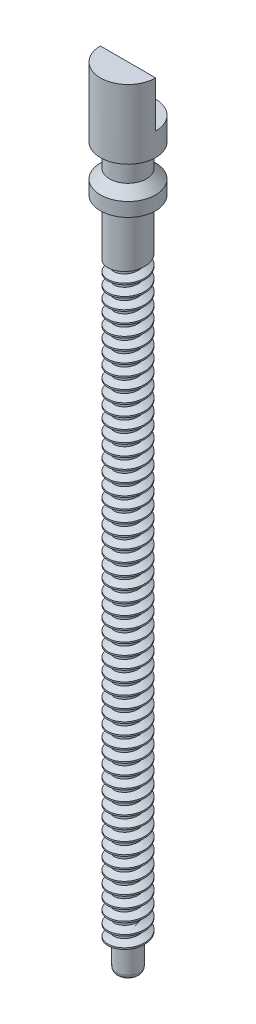
SolidWorks part; units mm, degrees
ref_plane "Front Plane" through (0, 0, 0) normal (0, 0, 1) x (1, 0, 0)
ref_plane "Top Plane" through (0, 0, 0) normal (0, 1, 0) x (1, 0, 0)
ref_plane "Right Plane" through (0, 0, 0) normal (1, 0, 0) x (0, 0, -1)
sketch "Sketch1" plane through (0, 0, 0) normal (0, 0, 1) x (1, 0, 0)
  line L0 (0, 0) -> (0, 17.1) construction
  line L1 (0, 0) -> (0.25, 0)
  line L2 (0.25, 0) -> (0.25, 0.6)
  line L3 (0.25, 0.6) -> (0.4, 0.6)
  line L4 (0.4, 0.6) -> (0.4, 13.6)
  line L5 (0.4, 13.6) -> (0.4, 14.6)
  line L6 (0.4, 14.6) -> (0.6, 14.6)
  line L7 (0.6, 14.6) -> (0.6, 14.9)
  line L8 (0.6, 14.9) -> (0.4, 15.1)
  line L9 (0.4, 15.1) -> (0.4, 15.6)
  line L10 (0.4, 15.6) -> (0.6, 15.6)
  line L11 (0.6, 15.6) -> (0.6, 17.1)
  line L12 (0.6, 17.1) -> (0, 17.1)
  line L13 (0, 17.1) -> (0, 0)
  dimension "D1" = 17.1
  dimension "D2" = 0.25
  dimension "D3" = 0.6
  dimension "D4" = 0.4
  dimension "D5" = 13
  dimension "D6" = 1
  dimension "D7" = 0.3
  dimension "D8" = 0.2
  dimension "D9" = 0.5
  dimension "D10" = 1.5
  dimension "D11" = 0.6
revolve "Revolve1" add sketch "Sketch1" angle 360 about L0
fillet "Fillet2" radius 0.1 1 edges at (0, 0, -0.25)
thread "Thread1" pitch 0.25 method cut profile "Thread Profile2" start angle 0, offset 1, length 0, pitch 0.25, diameter 0.8
ref_plane "Plane2" through (-0.4, 13.6, 0) normal (0, 0, 1) x (-1, 0, 0)
sketch "Thread Profile2" plane through (-0.4, 13.6, 0) normal (0, 0, 1) x (-1, 0, 0)
  line L0 (0, 0) -> (0, 0.25) construction
  line L11 (0, 0) -> (0, 0.2187)
  line L12 (0, 0.2187) -> (-0.1353, 0.1406)
  line L13 (-0.1353, 0.1406) -> (-0.1353, 0.0781)
  line L15 (-0.1353, 0.0781) -> (0, 0)
  line L17 (-0.1353, 0.1094) -> (0, 0.1094) construction
  point P2 (0, 0)
  dimension "Pitch" = 0.25
  dimension "Profile_Angle" = 60
  dimension "Profile_Land" = 0.0625
  dimension "Profile_Height" = 0.1353
sketch "Sketch3" plane through (0, 17.1, 0) normal (0, 1, 0) x (1, 0, 0)
  line L0 (-0.6, 0) -> (0.6, 0)
  arc A0 (-0.6, 0) -> (0.6, 0) centre (0, 0) cw
  circle A1 centre (0, 0) radius 0.6 construction
extrude "Cut-Extrude1" cut sketch "Sketch3" against normal blind 1
